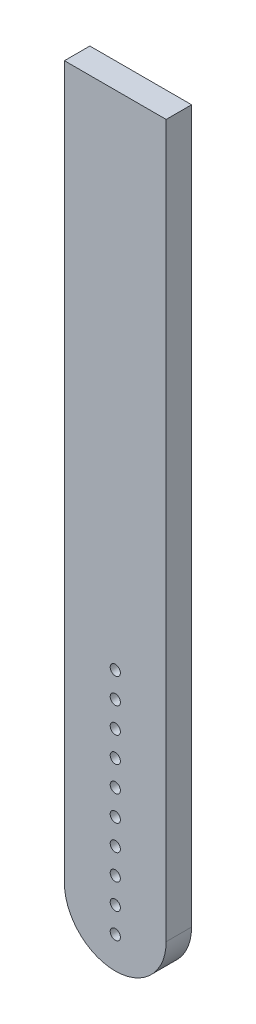
SolidWorks part; units mm, degrees
ref_plane "Front Plane" through (0, 0, 0) normal (0, 0, 1) x (1, 0, 0)
ref_plane "Top Plane" through (0, 0, 0) normal (0, 1, 0) x (1, 0, 0)
ref_plane "Right Plane" through (0, 0, 0) normal (1, 0, 0) x (0, 0, -1)
sketch "Sketch1" plane through (0, 0, 0) normal (0, 1, 0) x (1, 0, 0)
  line L1 (-20, 5) -> (20, 5)
  line L2 (-20, 5) -> (-20, -5)
  line L3 (-20, -5) -> (20, -5)
  line L4 (20, 5) -> (20, -5)
  line L5 (-20, 5) -> (20, -5) construction
  line L6 (-20, -5) -> (20, 5) construction
  point P0 (0, 0)
extrude "Boss-Extrude1" add sketch "Sketch1" along normal blind 300
fillet "Fillet1" radius 20 2 edges at (-20, 0, 0) (20, 0, 0)
sketch "Sketch2" plane through (0, 0, 5) normal (0, 0, 1) x (1, 0, 0)
  circle A0 centre (0, 12.5) radius 2
  dimension "D1" = 12.5
extrude "Cut-Extrude1" cut sketch "Sketch2" against normal through all
pattern_linear "LPattern1" count 10 spacing 10 along (0, 1, 0) of "Cut-Extrude1"
